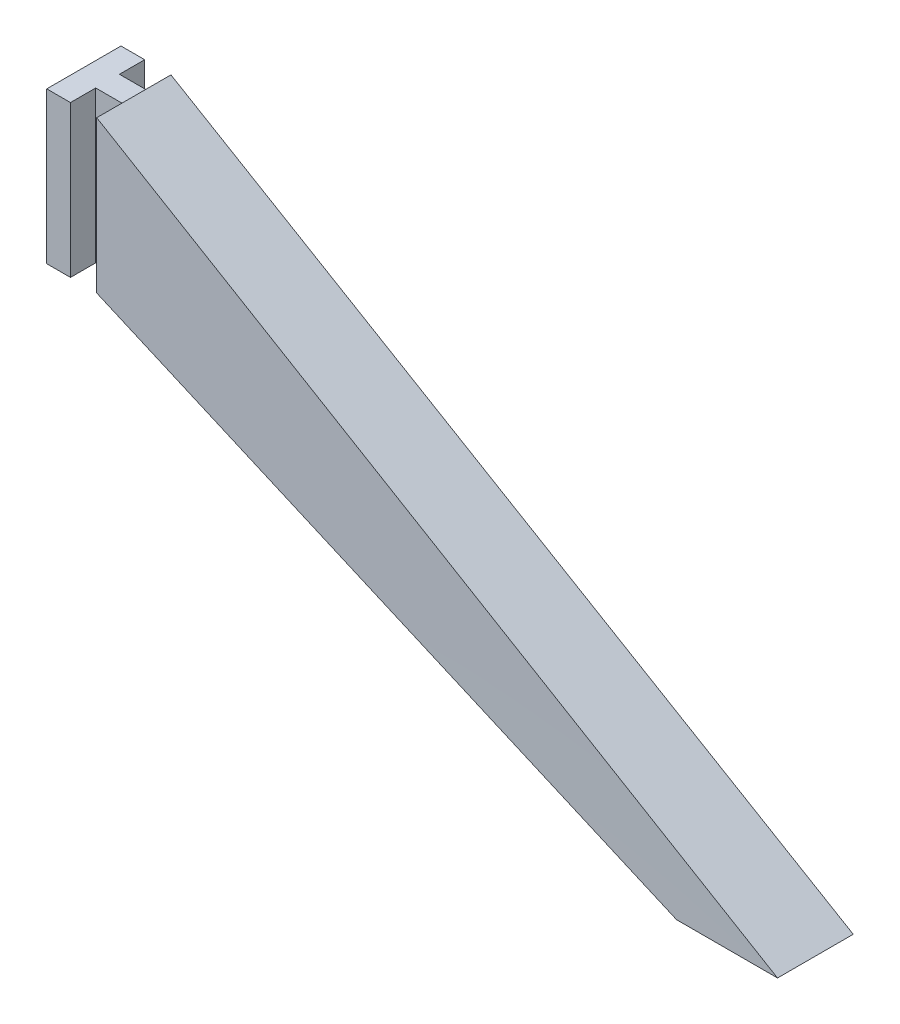
SolidWorks part; units mm, degrees
ref_plane "Front Plane" through (0, 0, 0) normal (0, 0, 1) x (1, 0, 0)
ref_plane "Top Plane" through (0, 0, 0) normal (0, 1, 0) x (1, 0, 0)
ref_plane "Right Plane" through (0, 0, 0) normal (1, 0, 0) x (0, 0, -1)
sketch "Sketch2" plane through (0, 0, 0) normal (0, 1, 0) x (1, 0, 0)
  line L0 (-9.9, 7.35) -> (-9.9, -7.35)
  line L1 (-9.9, -7.35) -> (-5.2, -7.35)
  line L2 (-5.2, -7.35) -> (-5.2, -2.35)
  line L3 (-5.2, -2.35) -> (0, -2.35)
  line L4 (0, -2.35) -> (0, 2.35)
  line L5 (0, 2.35) -> (-5.2, 2.35)
  line L6 (-5.2, 2.35) -> (-5.2, 7.35)
  line L7 (-5.2, 7.35) -> (-9.9, 7.35)
  point P2 (0, 0)
  dimension "D1" = 4.7
  dimension "D2" = 5.2
  dimension "D3" = 4.7
  dimension "D4" = 14.7
extrude "Boss-Extrude1" add sketch "Sketch2" along normal blind 30
sketch "Sketch3" plane through (0, 0, 0) normal (0, 0, 1) x (1, 0, 0)
  line L0 (0, 0) -> (125, 0)
  line L3 (125, 0) -> (125, 30)
  line L4 (125, 30) -> (0, 30)
  line L6 (0, 30) -> (0, 0)
  dimension "D4" = 125
ref_plane "Plane1" through (0, -50, 0) normal (0, 1, 0) x (1, 0, 0)
sketch "Sketch5" plane through (0, -50, 0) normal (0, 1, 0) x (-1, 0, 0)
  line L5 (-135, 7.5) -> (-115, 7.5)
  line L6 (-135, 7.5) -> (-135, -7.5)
  line L7 (-115, 7.5) -> (-115, -7.5)
  line L8 (-135, -7.5) -> (-115, -7.5)
  line L9 (0, 0) -> (-125, 0) construction
  point P1 (-125, 7.5)
  point P10 (-115, 0)
  dimension "D1" = 125
  dimension "D3" = 20
  dimension "D2" = 15
sketch "Sketch6" plane through (0, 0, 0) normal (1, 0, 0) x (0, 0, -1)
  line L11 (-7.35, 30) -> (7.35, 30)
  line L12 (-7.35, 30) -> (-7.35, -0.0748)
  line L13 (7.35, 30) -> (7.35, -0.0748)
  line L14 (-7.35, -0.0748) -> (7.35, -0.0748)
loft "Loft2" add profiles "Sketch6", "Sketch5" connector at (0, 30, 7.35) connector at (135, -50, 7.5)
